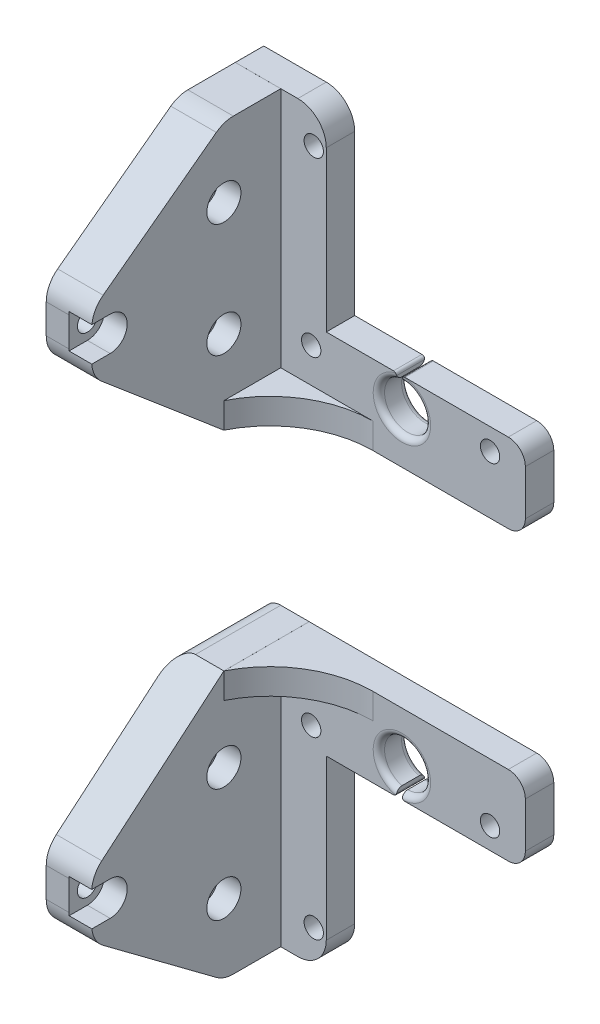
SolidWorks part; units mm, degrees
material "ABS"
ref_plane "Front Plane" through (0, 0, 0) normal (0, 0, 1) x (1, 0, 0)
ref_plane "Top Plane" through (0, 0, 0) normal (0, 1, 0) x (1, 0, 0)
ref_plane "Right Plane" through (0, 0, 0) normal (1, 0, 0) x (0, 0, -1)
ref_plane "Plane5" through (60, 0, 0) normal (1, 0, 0) x (0, 0, -1)
sketch "Sketch50" plane through (60, 0, 0) normal (1, 0, 0) x (0, 0, -1)
  line L0 (-38.2349, -28) -> (-38.2349, -38)
  line L1 (0, -55.3249) -> (-15, -55.3249)
  line L2 (0, -8.3249) -> (-15, -8.3249)
  line L4 (0, -55.3249) -> (0, -8.3249)
  line L5 (-15, -2.0171) -> (-15, -57.8143) construction
  line L9 (-38.2349, -28) -> (-15, -8.3249)
  line L10 (-38.2349, -38) -> (-15, -55.3249)
  circle A0 centre (-35, -33) radius 1.75
  circle A1 centre (-15, -23) radius 1.75
  circle A2 centre (-15, -43) radius 1.75
  dimension "D1" = 3.5
  dimension "D2" = 3.5
  dimension "D3" = 3.5
  dimension "D4" = 20
  dimension "D5" = 20
  dimension "D6" = 47
  dimension "D7" = 15
  dimension "D8" = 10
extrude "Extrude1" add sketch "Sketch50" along normal blind 8 separate body
sketch "Sketch52" plane through (0, 0, 0) normal (0, 0, -1) x (-1, 0, 0)
  line L0 (-60.0211, -55.3284) -> (-60.0211, -8.3284)
  line L1 (-111, -8.3284) -> (-111, -22.2806)
  line L2 (-60.0211, -8.3284) -> (-111, -8.3284)
  line L3 (-76, -22.2806) -> (-111, -22.2806)
  line L4 (-60.0211, -55.3284) -> (-76, -55.3284)
  line L5 (-76, -55.3249) -> (-76, -8.3249)
  line L6 (-76, -55.3284) -> (-76, -22.2806)
  circle A0 centre (-89.3, -17.2) radius 4.05
  circle A1 centre (-73.3515, -18.9313) radius 1.7
  circle A2 centre (-104.8, -18.5) radius 1.7
  circle A3 centre (-73.8015, -49.5086) radius 1.7
  point P3 (-113, -87.5802)
  point P9 (-74.0211, -54.9585)
  point P10 (-74.0211, -7.7617)
  dimension "D2" = 47
  dimension "D4" = 3.4
  dimension "D1" = 8
extrude "Extrude2" add sketch "Sketch52" against normal blind 5
fillet "Fillet1" radius 3 2 edges at (111, -22.2806, 2.5) (111, -8.3284, 2.5)
fillet "Fillet2" radius 5 1 edges at (76, -55.3284, 2.5)
sketch "Sketch54" plane through (0, -8.3284, 0) normal (0, 1, 0) x (1, 0, 0)
  line L0 (68, -5) -> (108, -5) construction
  line L1 (68, -15) -> (68, -5)
  line L2 (68, -15) -> (68, -38.2349) construction
  line L3 (68, 0) -> (68, -15) construction
  line L4 (68, -5) -> (84.1795, -5)
  arc A0 (84.1795, -5) -> (68, -15) centre (84.1795, -23.0887) ccw
extrude "Extrude3" add sketch "Sketch54" against normal blind 4.5
fillet "Fillet4" radius 5 3 edges at (64, -28, 38.2349) (64, -38, 38.2349) (64, -55.3249, 15)
fillet "Fillet5" radius 3 1 edges at (60, -8.3249, 7.5)
sketch "Sketch55" plane through (68, 0, 0) normal (1, 0, 0) x (0, 0, -1)
  line L0 (-35, -30) -> (-38.7879, -30)
  line L1 (-38.7879, -30) -> (-38.7879, -36)
  line L2 (-35, -36) -> (-38.7879, -36)
  arc A0 (-35, -36) -> (-35, -30) centre (-35, -33) ccw
  circle A1 centre (-15, -23) radius 3
  circle A2 centre (-15, -43) radius 3
  dimension "D1" = 6
  dimension "D2" = 6
  dimension "D3" = 6
extrude "Cut-Extrude3" cut sketch "Sketch55" against normal blind 4
fillet "Fillet6" radius 1 2 edges at (89.3, -13.15, 5) (89.3, -13.15, 0)
sketch "Sketch56" plane through (0, 0, 0) normal (0, 0, -1) x (-1, 0, 0)
  line L0 (-108, -22.2806) -> (-76, -22.2806) construction
  line L1 (-89.3173, -23.6005) -> (-88.3204, -23.6005)
  line L2 (-89.3173, -23.6005) -> (-89.3173, -20.9607)
  line L3 (-89.3173, -20.9607) -> (-88.3204, -20.9607)
  line L4 (-88.3204, -23.6005) -> (-88.3204, -20.9607)
  line L5 (-89.3173, -23.6005) -> (-88.3204, -20.9607) construction
  line L6 (-89.3173, -20.9607) -> (-88.3204, -23.6005) construction
  point P0 (-88.8189, -22.2806)
extrude "Cut-Extrude4" cut sketch "Sketch56" against normal up to surface (5 mm away) up to face at (89.3, -12.15, 5)
fillet "Fillet7" radius 0.5 2 edges at (88.3204, -22.2806, 2.5) (89.3173, -22.2806, 2.5)
ref_plane "Plane6" through (0, 10, 0) normal (0, 1, 0) x (1, 0, 0)
mirror "Mirror4" about plane through (0, 10, 0) normal (0, 1, 0) of bodies 133
